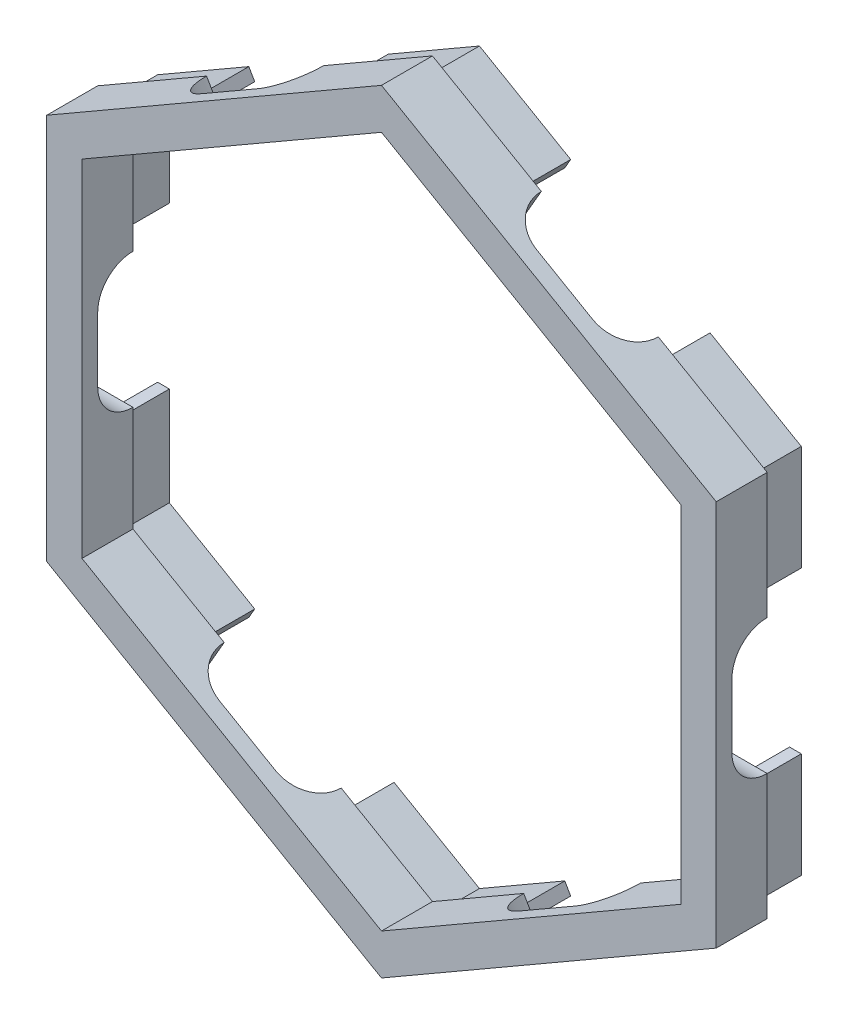
SolidWorks part; units mm, degrees
ref_plane "Front Plane" through (0, 0, 0) normal (1, 0, 0) x (0, 1, 0)
ref_plane "Top Plane" through (0, 0, 0) normal (0, 0, 1) x (0, 1, 0)
ref_plane "Right Plane" through (0, 0, 0) normal (0, 1, 0) x (-1, 0, 0)
sketch "Sketch1" plane through (0, 0, 0) normal (0, 0, 1) x (0, 1, 0)
  line L1 (29.4449, 0) -> (14.7224, 25.5)
  line L2 (14.7224, 25.5) -> (-14.7224, 25.5)
  line L3 (-14.7224, 25.5) -> (-29.4449, 0)
  line L4 (-29.4449, 0) -> (-14.7224, -25.5)
  line L5 (-14.7224, -25.5) -> (14.7224, -25.5)
  line L6 (14.7224, -25.5) -> (29.4449, 0)
  line L7 (32.909, 0) -> (16.4545, 28.5)
  line L8 (16.4545, 28.5) -> (-16.4545, 28.5)
  line L9 (-16.4545, 28.5) -> (-32.909, 0)
  line L10 (-32.909, 0) -> (-16.4545, -28.5)
  line L11 (-16.4545, -28.5) -> (16.4545, -28.5)
  line L12 (16.4545, -28.5) -> (32.909, 0)
  circle A0 centre (0, 0) radius 25.5 construction
  circle A1 centre (0, 0) radius 28.5 construction
  dimension "D1" = 51
  dimension "D2" = 3
extrude "Boss-Extrude1" add sketch "Sketch1" along normal blind 4.34
sketch "Sketch2" plane through (28.5, 0, 0) normal (1, 0, 0) x (0, 1, 0)
  line L0 (-2.75, 0) -> (2.75, 0) construction
  line L1 (-16.4545, 0) -> (16.4545, 0) construction
  line L2 (-2.75, 3) -> (2.75, 3)
  line L3 (-2.75, -3) -> (2.75, -3)
  line L5 (-16.4545, 4.34) -> (16.4545, 4.34) construction
  arc A0 (-2.75, 3) -> (-2.75, -3) centre (-2.75, 0) ccw
  arc A1 (2.75, -3) -> (2.75, 3) centre (2.75, 0) ccw
  point P4 (0, 0)
  point P9 (-5.75, 0)
  point P10 (5.75, 0)
  point P11 (0, 0)
  point P13 (-2.75, 0)
  dimension "D1" = 6
  dimension "D2" = 11.5
extrude "Cut-Extrude1" cut sketch "Sketch2" against normal through all
sketch "Sketch3" plane through (14.25, 24.6817, 0) normal (0.5, 0.866, 0) x (-0.866, 0.5, 0)
  line L0 (-2.75, 0) -> (2.75, 0) construction
  line L1 (-2.75, 3) -> (2.75, 3)
  line L2 (-2.75, -3) -> (2.75, -3)
  line L3 (-16.4545, 0) -> (16.4545, 0) construction
  arc A0 (-2.75, 3) -> (-2.75, -3) centre (-2.75, 0) ccw
  arc A1 (2.75, -3) -> (2.75, 3) centre (2.75, 0) ccw
  point P2 (0, 0)
  point P7 (-5.75, 0)
  point P8 (5.75, 0)
  point P11 (0, 0)
  point P12 (0, 0)
  dimension "D1" = 6
  dimension "D2" = 11.5
extrude "Cut-Extrude2" cut sketch "Sketch3" against normal up to surface (57 mm away) up to face at (-14.25, -24.6817, 2.17)
sketch "Sketch4" plane through (-14.25, 24.6817, 0) normal (-0.5, 0.866, 0) x (-0.866, -0.5, 0)
  line L0 (-2.75, 0) -> (2.75, 0) construction
  line L1 (-2.75, 3) -> (2.75, 3)
  line L2 (-2.75, -3) -> (2.75, -3)
  line L3 (-16.4545, 0) -> (16.4545, 0) construction
  arc A0 (-2.75, 3) -> (-2.75, -3) centre (-2.75, 0) ccw
  arc A1 (2.75, -3) -> (2.75, 3) centre (2.75, 0) ccw
  point P2 (0, 0)
  point P7 (-5.75, 0)
  point P8 (5.75, 0)
  point P9 (0, 0)
  point P13 (0, 0)
  point P14 (2.75, 0)
  dimension "D1" = 6
  dimension "D2" = 11.5
extrude "Cut-Extrude3" cut sketch "Sketch4" against normal up to surface (57 mm away) up to face at (14.25, -24.6817, 2.17)
sketch "Sketch5" plane through (0, 0, 0) normal (0, 0, 1) x (0, 1, 0)
  line L0 (-20.3041, 19.6323) -> (-19.4381, 19.1323)
  line L1 (-20.3041, 19.6323) -> (-15.8194, 27.4)
  line L2 (-19.4381, 19.1323) -> (-15.242, 26.4)
  line L3 (-16.4545, 28.5) -> (-14.7224, 25.5) construction
  line L4 (-6.85, 27.4) -> (-15.8194, 27.4)
  line L5 (-6.85, 27.4) -> (-6.85, 26.4)
  line L6 (-6.85, 26.4) -> (-15.242, 26.4)
  line L7 (20.3041, 19.6323) -> (15.8194, 27.4)
  line L8 (19.4381, 19.1323) -> (15.242, 26.4)
  line L9 (20.3041, 19.6323) -> (19.4381, 19.1323)
  line L10 (-5.75, 28.5) -> (-5.75, 25.5) construction
  line L11 (-19.2086, 17.7296) -> (-21.8067, 19.2296) construction
  line L12 (-5.75, 28.5) -> (-16.4545, 28.5) construction
  line L13 (6.85, 27.4) -> (15.8194, 27.4)
  line L14 (6.85, 26.4) -> (15.242, 26.4)
  line L15 (6.85, 27.4) -> (6.85, 26.4)
  line L16 (27.1541, -7.7677) -> (31.6388, 0)
  line L17 (26.2881, -7.2677) -> (30.4841, 0)
  line L18 (27.1541, -7.7677) -> (26.2881, -7.2677)
  line L19 (27.1541, 7.7677) -> (31.6388, 0)
  line L20 (26.2881, 7.2677) -> (30.4841, 0)
  line L21 (27.1541, 7.7677) -> (26.2881, 7.2677)
  line L22 (6.85, -27.4) -> (15.8194, -27.4)
  line L23 (6.85, -26.4) -> (15.242, -26.4)
  line L24 (6.85, -27.4) -> (6.85, -26.4)
  line L25 (20.3041, -19.6323) -> (15.8194, -27.4)
  line L26 (19.4381, -19.1323) -> (15.242, -26.4)
  line L27 (20.3041, -19.6323) -> (19.4381, -19.1323)
  line L28 (-20.3041, -19.6323) -> (-15.8194, -27.4)
  line L29 (-19.4381, -19.1323) -> (-15.242, -26.4)
  line L30 (-20.3041, -19.6323) -> (-19.4381, -19.1323)
  line L31 (-6.85, -27.4) -> (-15.8194, -27.4)
  line L32 (-6.85, -26.4) -> (-15.242, -26.4)
  line L33 (-6.85, -27.4) -> (-6.85, -26.4)
  line L34 (-27.1541, 7.7677) -> (-31.6388, 0)
  line L35 (-26.2881, 7.2677) -> (-30.4841, 0)
  line L36 (-27.1541, 7.7677) -> (-26.2881, 7.2677)
  line L37 (-27.1541, -7.7677) -> (-31.6388, 0)
  line L38 (-26.2881, -7.2677) -> (-30.4841, 0)
  line L39 (-27.1541, -7.7677) -> (-26.2881, -7.2677)
  point P8 (-16.4545, 28.5)
  point P9 (-14.7224, 25.5)
  point P51 (0, 0)
  dimension "D1" = 1.1
  dimension "D2" = 6
  dimension "D4" = 1
  dimension "D6" = 1.1
extrude "Boss-Extrude2" add sketch "Sketch5" against normal blind 4
